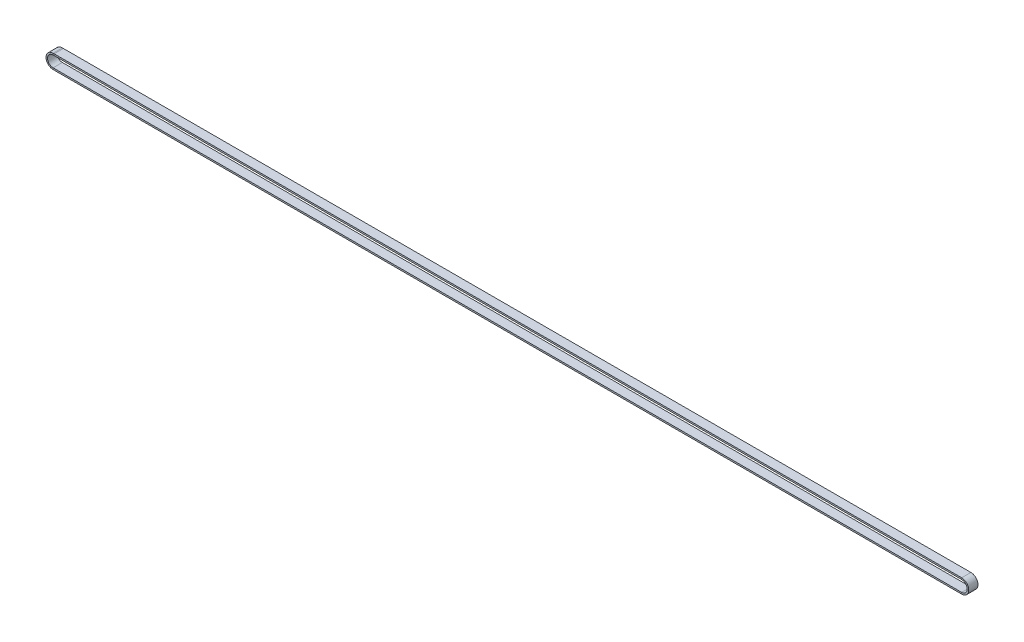
SolidWorks part; units mm, degrees
ref_plane "Front Plane" through (0, 0, 0) normal (0, 0, 1) x (1, 0, 0)
ref_plane "Top Plane" through (0, 0, 0) normal (0, 1, 0) x (1, 0, 0)
ref_plane "Right Plane" through (0, 0, 0) normal (1, 0, 0) x (0, 0, -1)
sketch "Sketch2" plane through (0, 0, -90.9834) normal (0, 0, 1) x (1, 0, 0)
  line L0 (0, 0) -> (1, 0) construction
  line L1 (0, 0) -> (0, 1) construction
  line L2 (-1, 41.3708) -> (883.5206, 41.3708)
  line L3 (883.5206, 27.5708) -> (-1, 27.5708)
  arc A0 (-1, 27.5708) -> (-1, 41.3708) centre (-1, 34.4708) cw
  arc A1 (883.5206, 41.3708) -> (883.5206, 27.5708) centre (883.5206, 34.4708) cw
sketch "Sketch3" plane through (0, 0, 0) normal (1, 0, 0) x (0, 0, -1)
  line L1 (90.9834, 39.8708) -> (81.9834, 39.8708)
  line L2 (90.9834, 39.8708) -> (90.9834, 41.3708)
  line L3 (90.9834, 41.3708) -> (81.9834, 41.3708)
  line L4 (81.9834, 39.8708) -> (81.9834, 41.3708)
  dimension "D1" = 9
  dimension "D2" = 1.5
sweep "Sweep1" add profiles "Sketch3" path "Sketch2"
